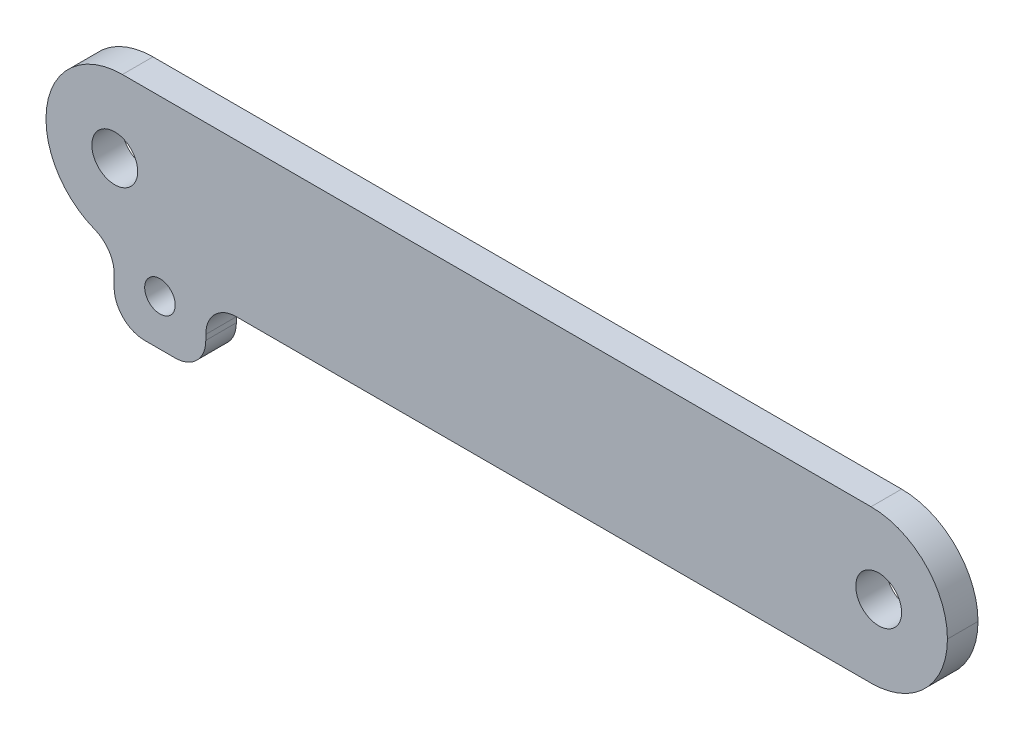
SolidWorks part; units mm, degrees
ref_plane "Front" through (0, 0, 0) normal (0, 0, 1) x (1, 0, 0)
ref_plane "Top" through (0, 0, 0) normal (0, 1, 0) x (1, 0, 0)
ref_plane "Right" through (0, 0, 0) normal (1, 0, 0) x (0, 0, -1)
sketch "Sketch1" plane through (0, 0, 0) normal (0, 0, 1) x (1, 0, 0)
  line L0 (4.5, 5) -> (7.4583, -1.3442) construction
  line L2 (0, 0) -> (0, 10)
  line L3 (0, 10) -> (59, 10)
  line L4 (59, 0) -> (59, 10)
  line L5 (4.5, 5) -> (14.156, 5) construction
  line L6 (0, 5) -> (59, 5) construction
  line L8 (4.4583, -4.3442) -> (10.4583, -4.3442)
  line L9 (10.4583, -4.3442) -> (10.4583, 0)
  line L10 (10.4583, 0) -> (59, 0)
  line L11 (0, 0) -> (4.4583, 0)
  line L12 (4.4583, 0) -> (4.4583, -4.3442)
  circle A0 centre (4.5, 5) radius 1.5
  circle A1 centre (54.5, 5) radius 1.5
  circle A2 centre (7.4583, -1.3442) radius 1
  dimension "D3" = 3
  dimension "D4" = 3
  dimension "D5" = 3
  dimension "D6" = 7
  dimension "D7" = 3
  dimension "D9" = 2
  dimension "D10" = 2
  dimension "D2" = 10
  dimension "D8" = 115
  dimension "D11" = 2
  dimension "D12" = 2
  dimension "D13" = 50
extrude "Boss-Extrude1" add sketch "Sketch1" along normal blind 2
fillet "Fillet2" radius 5 4 edges at (59, 0, 1) (59, 10, 1) (0, 10, 1) (0, 0, 1)
fillet "Fillet3" radius 2 4 edges at (10.4583, -4.3442, 1) (10.4583, 0, 1) (4.4583, -4.3442, 1) (4.4583, 0, 1)
